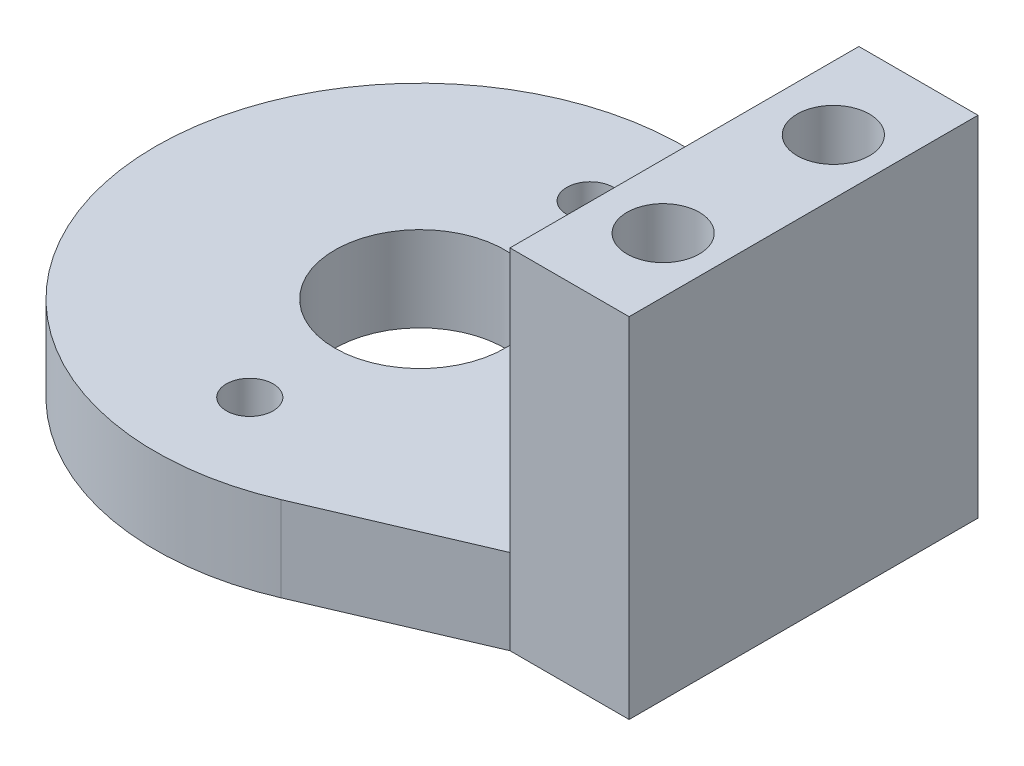
SolidWorks part; units mm, degrees
ref_plane "Front" through (0, 0, 0) normal (0, 0, 1) x (1, 0, 0)
ref_plane "Top" through (0, 0, 0) normal (0, 1, 0) x (1, 0, 0)
ref_plane "Right" through (0, 0, 0) normal (1, 0, 0) x (0, 0, -1)
sketch "Sketch1" plane through (0, 0, 0) normal (0, 1, 0) x (1, 0, 0)
  line L1 (0, 0) -> (7, 0)
  line L2 (0, 0) -> (0, -20.5)
  line L3 (0, -20.5) -> (7, -20.5)
  line L4 (7, 0) -> (7, -20.5)
  dimension "D1" = 7
  dimension "D2" = 20.5
extrude "mountingBase" add sketch "Sketch1" along normal blind 20.5003
sketch "Sketch2" plane through (0, 20.5003, 0) normal (0, 1, 0) x (1, 0, 0)
  line L0 (0, 0) -> (0, -20.5) construction
  line L1 (0, -10.25) -> (7, -10.25) construction
  line L2 (7, -20.5) -> (7, 0) construction
  line L3 (7, 0) -> (0, 0) construction
  circle A0 centre (3.75, -5.25) radius 2.125
  circle A1 centre (3.75, -15.25) radius 2.125
  dimension "D2" = 4.25
  dimension "D1" = 3.75
  dimension "D3" = 5.25
extrude "mountingHoles" cut sketch "Sketch2" against normal through all
sketch "Sketch3" plane through (0, 0, 0) normal (0, 1, 0) x (1, 0, 0)
  line L0 (0, 0) -> (0, -20.5) construction
  line L1 (0, 0) -> (-9.4224, 4.0351)
  line L2 (0, -20.5) -> (-9.4224, -24.5351)
  line L3 (0, 0) -> (0, -20.5)
  arc A0 (-9.4224, 4.0351) -> (-9.4224, -24.5351) centre (-15.5398, -10.25) ccw
  point P4 (0, -10.25)
  dimension "D1" = 15.5398
extrude "hornTab" add sketch "Sketch3" along normal blind 5
sketch "Sketch4" plane through (0, 5, 0) normal (0, 1, 0) x (1, 0, 0)
  line L0 (-15.5398, -10.25) -> (-31.0797, -10.25) construction
  circle A0 centre (-15.5398, -10.25) radius 15.5398 construction
  arc A1 (-9.4224, 4.0351) -> (-9.4224, -24.5351) centre (-15.5398, -10.25) ccw construction
  circle A2 centre (-15.5398, -0.25) radius 1.375
  circle A3 centre (-15.5398, -20.25) radius 1.375
  circle A4 centre (-15.5398, -10.25) radius 5
  dimension "D1" = 2.75
  dimension "D3" = 10
  dimension "D2" = 10
extrude "hornMountingHoles" cut sketch "Sketch4" against normal blind 5
